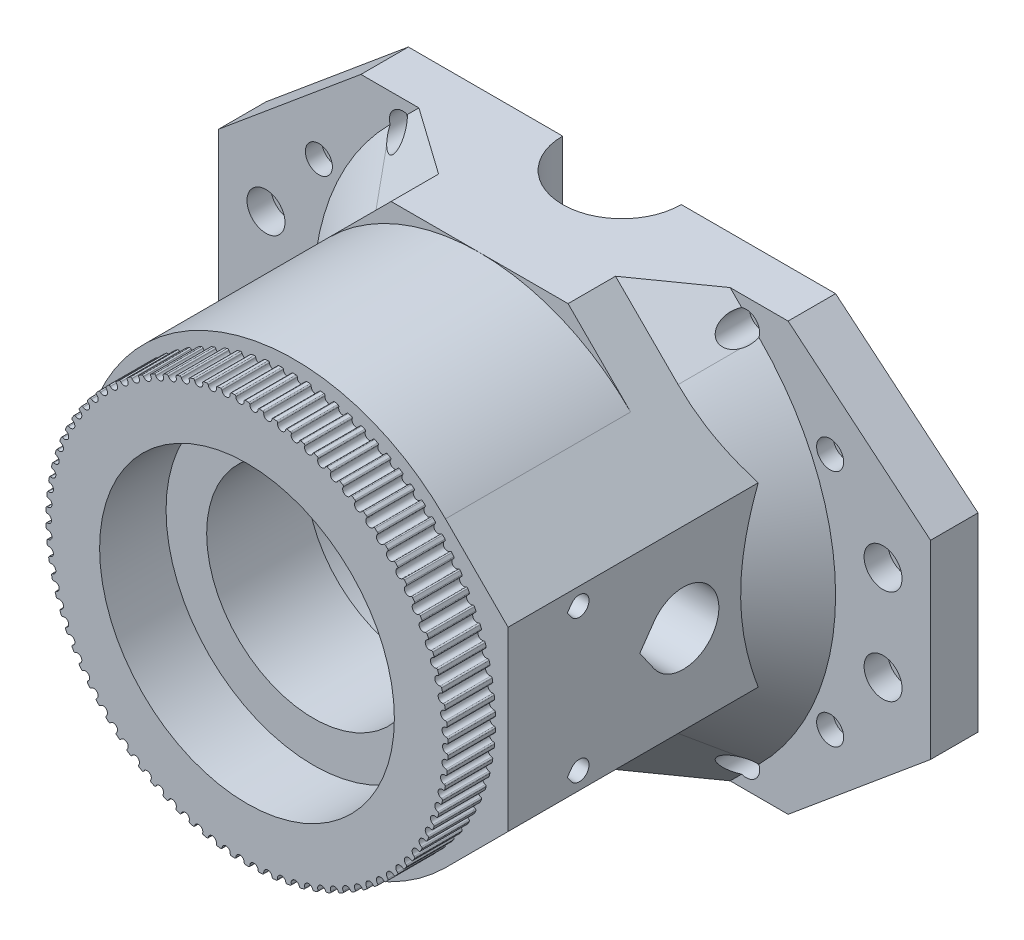
SolidWorks part; units mm, degrees
ref_plane "Front Plane" through (0, 0, 0) normal (1, 0, 0) x (0, 1, 0)
ref_plane "Top Plane" through (0, 0, 0) normal (0, 0, 1) x (0, 1, 0)
ref_plane "Right Plane" through (0, 0, 0) normal (0, 1, 0) x (-1, 0, 0)
sketch "Sketch1" plane through (0, 0, 0) normal (1, 0, 0) x (0, 1, 0)
  line L0 (-45, -80) -> (45, -80)
  line L1 (-31, 0) -> (31, 0)
  line L2 (-31, 0) -> (-31, -14)
  line L3 (-31, -14) -> (31, -14)
  line L4 (31, 0) -> (31, -14)
  line L5 (-31, 0) -> (31, -14) construction
  line L6 (-31, -14) -> (31, 0) construction
  line L7 (-31, -36) -> (31, -36)
  line L8 (-31, -36) -> (-31, -50)
  line L9 (-31, -50) -> (31, -50)
  line L10 (31, -36) -> (31, -50)
  line L11 (-31, -36) -> (31, -50) construction
  line L12 (-31, -50) -> (31, -36) construction
  line L13 (45, -80) -> (45, -1)
  line L14 (45, -1) -> (31, -1)
  line L15 (-31, -1) -> (-45, -1)
  line L16 (-45, -1) -> (-45, -80)
  point P0 (0, -7)
  point P5 (0, -43)
  point P16 (0, 0)
  dimension "D1" = 62
  dimension "D2" = 62
  dimension "D3" = 14
  dimension "D4" = 14
  dimension "D5" = 30
  dimension "D6" = 1
  dimension "D7" = 22
  dimension "D8" = 90
sketch "Sketch2" plane through (0, 0, 0) normal (0, 0, 1) x (0, 1, 0)
  line L0 (-45, 45) -> (-20, 75)
  line L1 (-20, 75) -> (20, 75)
  line L2 (45, 45) -> (-45, 45)
  line L3 (45, 45) -> (45, -45)
  line L4 (45, -45) -> (-45, -45)
  line L5 (-45, 45) -> (-45, -45)
  line L6 (45, 45) -> (-45, -45) construction
  line L7 (45, -45) -> (-45, 45) construction
  line L8 (20, 75) -> (45, 45)
  line L9 (-45, -45) -> (-20, -75)
  line L10 (-20, -75) -> (20, -75)
  line L11 (20, -75) -> (45, -45)
  line L12 (0, 75) -> (0, -75) construction
  line L13 (-45, -18.6396) -> (-18.6396, -45)
  line L14 (-18.6396, 45) -> (-45, 18.6396)
  line L15 (45, 18.6396) -> (18.6396, 45)
  line L16 (18.6396, -45) -> (45, -18.6396)
  circle A0 centre (0, 0) radius 45
  circle A1 centre (0, 0) radius 31.05
  circle A2 centre (0, 0) radius 22.5
  point P15 (0, 0)
  point P27 (0, 0)
  dimension "D1" = 90
  dimension "D2" = 62.1
  dimension "D3" = 45
  dimension "D4" = 150
  dimension "D5" = 40
  dimension "D6" = 4
  dimension "D7" = 45
extrude "Boss-Extrude1" add sketch "Sketch2" against normal up to vertex (80 mm away) from offset 11 contours A0 A1 | A1 A2 region at (-40.3987, 16.7337, 0) region at (0, -30.1718, 0) up to point (0, -45, -80) offset against normal yes
extrude "Boss-Extrude2" add sketch "Sketch2<3>" along normal blind 10 from surface contours A0 L5 L4 | A0 L2 L5 | A0 L4 L3 | A0 L3 L2 | L10 L11 L4 L9 | L8 L1 L0 L2 | A0 L13 L4 | A0 L5 L13 | A0 L4 | A0 L3 | A0 L2 L14 | A0 L14 L5 | A0 L3 L15 | A0 L15 L2 region at (-58.0769, 0, 0) region at (-36.2132, -36.2132, 0) region at (-42.2926, -17.5182, 0) region at (-17.5182, -42.2926, 0) region at (-42.2926, 17.5182, 0) region at (17.5182, -42.2926, 0) region at (-36.2132, 36.2132, 0) region at (-17.5182, 42.2926, 0) region at (36.2132, -36.2132, 0) region at (42.2926, -17.5182, 0) region at (17.5182, 42.2926, 0) region at (58.0769, 0, 0) region at (42.2926, 17.5182, 0) region at (36.2132, 36.2132, 0) starting at face at (45, 0, -80)
sketch "Sketch2<3>" plane through (0, 0, 0) normal (0, 0, 1) x (0, 1, 0) same geometry as "Sketch2"
extrude "Boss-Extrude4" add sketch "Sketch2<6>" along normal blind 20 from surface contours A0 L5 | A0 L5 L13 | A0 L16 L3 | A0 L3 L15 region at (-17.5182, -42.2926, 0) region at (17.5182, -42.2926, 0) region at (-17.5182, 42.2926, 0) region at (17.5182, 42.2926, 0) starting at face at (-47.5, 0, -70)
sketch "Sketch2<6>" plane through (0, 0, 0) normal (0, 0, 1) x (0, 1, 0) same geometry as "Sketch2"
sketch "Sketch5" plane through (0, -45, 0) normal (0, -1, 0) x (1, 0, 0)
  line L0 (-45, -80) -> (45, -80) construction
  circle A0 centre (0, -80) radius 12.5
  line M9 (-45, -80) -> (45, -80)
  dimension "D1" = 25
extrude "Cut-Extrude3" cut sketch "Sketch5" against normal through all contours A0 M9 region at (0, -45, -74.6948)
sketch "Sketch6" plane through (0, 0, -70) normal (0, 0, 1) x (1, 0, 0)
  line L0 (-65, 10) -> (-65, -10) construction
  line L1 (0, 0) -> (-99.7082, 0) construction
  line L2 (65, 10) -> (65, -10) construction
  line L3 (75, -20) -> (75, 20) construction
  line L4 (-75, -20) -> (-75, 20) construction
  circle A0 centre (65, 10) radius 4
  circle A1 centre (65, 10) radius 2.05
  circle A2 centre (-65, 10) radius 2.05
  circle A3 centre (-65, 10) radius 4
  circle A4 centre (-65, -10) radius 2.05
  circle A5 centre (-65, -10) radius 4
  circle A6 centre (65, -10) radius 2.05
  circle A7 centre (65, -10) radius 4
  point P3 (-65, 0)
  point P9 (65, 0)
  dimension "D4" = 8
  dimension "D5" = 4.1
  dimension "D1" = 20
  dimension "D2" = 10
  dimension "D3" = 10
  dimension "D6" = 2
  dimension "D7" = 2
extrude "Cut-Extrude4" cut sketch "Sketch6" against normal through all contours A1 | A4 | A2 | A6
extrude "Cut-Extrude5" cut sketch "Sketch6<4>" against normal blind 5
sketch "Sketch6<4>" plane through (0, 0, -70) normal (0, 0, 1) x (1, 0, 0) same geometry as "Sketch6"
extrude "Cut-Extrude1" cut sketch "Sketch2<4>" against normal blind 15 contours A1
sketch "Sketch2<4>" plane through (0, 0, 0) normal (0, 0, 1) x (0, 1, 0) same geometry as "Sketch2"
extrude "Cut-Extrude2" cut sketch "Sketch2<5>" against normal through all from vertex contours A1 starting at point (0, -31, -36)
sketch "Sketch2<5>" plane through (0, 0, 0) normal (0, 0, 1) x (0, 1, 0) same geometry as "Sketch2"
sketch "Sketch7" plane through (0, 0, -70) normal (0, 0, 1) x (1, 0, 0)
  line L0 (-75, 20) -> (75, 20) construction
  line L1 (-45, 45) -> (-18.6396, 45) construction
  line L2 (-45, 45) -> (0, 45) construction
  line L3 (-30, 45) -> (-60, 20) construction
  line L4 (-75, 20) -> (-45, 45) construction
  line L5 (0, 13.0372) -> (0, -13.0372) construction
  line L6 (-13.0372, 0) -> (13.0372, 0) construction
  line L7 (30, 45) -> (60, 20) construction
  line L8 (30, -45) -> (60, -20) construction
  line L9 (-30, -45) -> (-60, -20) construction
  circle A0 centre (-53.8542, 25.1215) radius 1.6
  circle A1 centre (-53.8542, 25.1215) radius 2.85
  circle A2 centre (-36.1458, 39.8785) radius 2.85
  circle A3 centre (-36.1458, 39.8785) radius 1.6
  circle A4 centre (36.1458, 39.8785) radius 1.6
  circle A5 centre (36.1458, 39.8785) radius 2.85
  circle A6 centre (53.8542, 25.1215) radius 2.85
  circle A7 centre (53.8542, 25.1215) radius 1.6
  circle A8 centre (53.8542, -25.1215) radius 1.6
  circle A9 centre (53.8542, -25.1215) radius 2.85
  circle A10 centre (36.1458, -39.8785) radius 2.85
  circle A11 centre (36.1458, -39.8785) radius 1.6
  circle A12 centre (-36.1458, -39.8785) radius 1.6
  circle A13 centre (-36.1458, -39.8785) radius 2.85
  circle A14 centre (-53.8542, -25.1215) radius 2.85
  circle A15 centre (-53.8542, -25.1215) radius 1.6
  circle A16 centre (-36.1458, -39.8785) radius 5.5
  circle A17 centre (36.1458, -39.8785) radius 5.5
  point P23 (0, 0)
  point P26 (0, 0)
  dimension "D2" = 5.7
  dimension "D3" = 3.2
  dimension "D6" = 3.2
  dimension "D7" = 5.7
  dimension "D8" = 11
  dimension "D9" = 11
  dimension "D1" = 15
  dimension "D4" = 8
  dimension "D5" = 8
extrude "Cut-Extrude6" cut sketch "Sketch7" against normal through all contours A15 | A0 | A3 | A4 | A7 | A8 | A11 | A12
extrude "Cut-Extrude7" cut sketch "Sketch7<3>" against normal blind 3.5 contours A14 | A1 | A2 | A5 | A6 | A9 | A10 | A13
sketch "Sketch7<3>" plane through (0, 0, -70) normal (0, 0, 1) x (1, 0, 0) same geometry as "Sketch7"
chamfer "Chamfer2" distance 10 angle 45 6 edges at (25.2297, -38.4099, -70) (25.2297, 38.4099, -70) (45, 0, -70) (-25.2297, 38.4099, -70) (-25.2297, -38.4099, -70) (-45, 0, -70)
extrude "Boss-Extrude6" add sketch "Sketch2<7>" against normal up to surface (70 mm away) from surface contours A0 L13 L4 | A0 L4 L16 region at (42.2926, -17.5182, 0) region at (42.2926, 17.5182, 0) up to face at (56.7042, -25.1215, -70) starting at face at (31.05, 0, -11)
sketch "Sketch2<7>" plane through (0, 0, 0) normal (0, 0, 1) x (0, 1, 0) same geometry as "Sketch2"
sketch "Sketch8" plane through (45, 0, 0) normal (1, 0, 0) x (0, 1, 0)
  line L0 (-15, -26) -> (-9.9, -26) construction
  line L1 (15, -26) -> (20.2, -26) construction
  line L2 (-15, -26) -> (-20.2, -26) construction
  line L3 (-9.9, -26) -> (15, -26) construction
  line L4 (-9.9, -26) -> (-9.9, -11) construction
  line L5 (18.6396, -11) -> (-18.6396, -11) construction
  line L6 (-20.2, -26) -> (-20.2, -11)
  line L7 (-31.8198, -11) -> (-18.6396, -11) construction
  line L8 (20.2, -26) -> (20.2, -11)
  line L9 (18.6396, -11) -> (31.8198, -11) construction
  line L10 (-14.0823, -24.6894) -> (-15, -24.0468)
  line L11 (-16.1758, -24.3207) -> (-15, -23.4974)
  line L12 (-15.9177, -24.6894) -> (-15, -24.0468)
  line L13 (-13.8242, -24.3207) -> (-15, -23.4974)
  line L14 (-15, -26) -> (-15, -23.4974) construction
  line L15 (16.1758, -24.3207) -> (15, -23.4974)
  line L16 (15, -26) -> (15, -23.4974) construction
  line L17 (14.0823, -24.6894) -> (15, -24.0468)
  line L18 (13.8242, -24.3207) -> (15, -23.4974)
  line L19 (15.9177, -24.6894) -> (15, -24.0468)
  line L20 (-20.2, -11) -> (20.2, -11)
  line L21 (-20.2, -26) -> (-20.2, -32.9)
  line L22 (20.2, -26) -> (20.2, -32.9)
  line L23 (-20.2, -32.9) -> (20.2, -32.9)
  line L24 (0, -47.9) -> (0, -38.7442) construction
  line L25 (-4.3018, -41.7564) -> (0, -38.7442)
  line L26 (4.3018, -41.7564) -> (0, -38.7442)
  arc A0 (-16.1758, -24.3207) -> (-13.8242, -24.3207) centre (-15, -26) ccw
  arc A1 (-15.9177, -24.6894) -> (-14.0823, -24.6894) centre (-15, -26) ccw
  arc A2 (14.0823, -24.6894) -> (15.9177, -24.6894) centre (15, -26) ccw
  arc A3 (13.8242, -24.3207) -> (16.1758, -24.3207) centre (15, -26) ccw
  arc A4 (-4.3018, -41.7564) -> (4.3018, -41.7564) centre (0, -47.9) ccw
  point P29 (0, -11)
  point P35 (0, 0)
  dimension "D6" = 3.2
  dimension "D7" = 4.1
  dimension "D10" = 3.2
  dimension "D11" = 4.1
  dimension "D15" = 15
  dimension "D1" = 15
  dimension "D2" = 24.9
  dimension "D3" = 5.2
  dimension "D4" = 5.1
  dimension "D5" = 5.2
  dimension "D8" = 55
  dimension "D9" = 55
  dimension "D12" = 55
  dimension "D13" = 55
  dimension "D14" = 6.9
  dimension "D16" = 15
  dimension "D17" = 55
sketch "Sketch3" plane through (0, 0, -11) normal (0, 0, 1) x (1, 0, 0)
  line L0 (0, 0) -> (0, 42.3568)
  line L1 (0, 0) -> (1.4374, 41.1617) construction
  line L2 (0, 0) -> (2.9547, 42.2537)
  line L3 (1.4374, 41.1617) -> (1.4678, 42.0312) construction
  arc A0 (0.6589, 42.3517) -> (2.297, 42.2945) centre (1.4678, 42.0312) ccw
  arc A1 (0, 42.3568) -> (0.6589, 42.3517) centre (0, 0) cw
  arc A2 (2.297, 42.2945) -> (2.9547, 42.2537) centre (0, 0) cw
  arc A3 (0, 31.05) -> (2.1659, 30.9744) centre (0, 0) cw
  circle A4 centre (0, 0) radius 31.05 construction
  circle M5 centre (0, 0) radius 31.05
  dimension "D1" = 42.3568
  dimension "D2" = 2
  dimension "D3" = 2
  dimension "D4" = 42.3568
  dimension "D5" = 41.1868
  dimension "D6" = 0.87
extrude "Boss-Extrude3" add sketch "Sketch3" along normal blind 10 contours A2 A0 A1 L0 L2 M5 region at (1.2803, 36.6619, -11)
fillet "Fillet1" radius 0.26 2 edges at (2.297, 42.2945, -6) (0.6589, 42.3517, -6)
pattern_circular "CirPattern1" count 90 over 360 about axis through (0, 0, -80) along (0, 0, 1) of "Fillet1", "Boss-Extrude3" reverse direction yes
extrude "Cut-Extrude9" cut sketch "Sketch8" against normal blind 7 contours A0 L13 L11 | A3 L15 L18
extrude "Cut-Extrude10" cut sketch "Sketch8<3>" against normal blind 3 from surface contours A1 L10 L12 | A2 L19 L17 starting at face at (38, -15, -25.2894)
sketch "Sketch8<3>" plane through (45, 0, 0) normal (1, 0, 0) x (0, 1, 0) same geometry as "Sketch8"
extrude "Cut-Extrude11" cut sketch "Sketch8<4>" against normal blind 45 contours A4 L26 L25
sketch "Sketch8<4>" plane through (45, 0, 0) normal (1, 0, 0) x (0, 1, 0) same geometry as "Sketch8"
equation "\"D1@Sketch3\"=3 * 90 / PI / 2-0.615"
equation "\"D3@Sketch3\"=\"D2@Sketch3\""
equation "\"D4@Sketch3\"=\"D1@Sketch3\""
equation "\"D5@Sketch3\"=\"D1@Sketch3\"-1.17"
